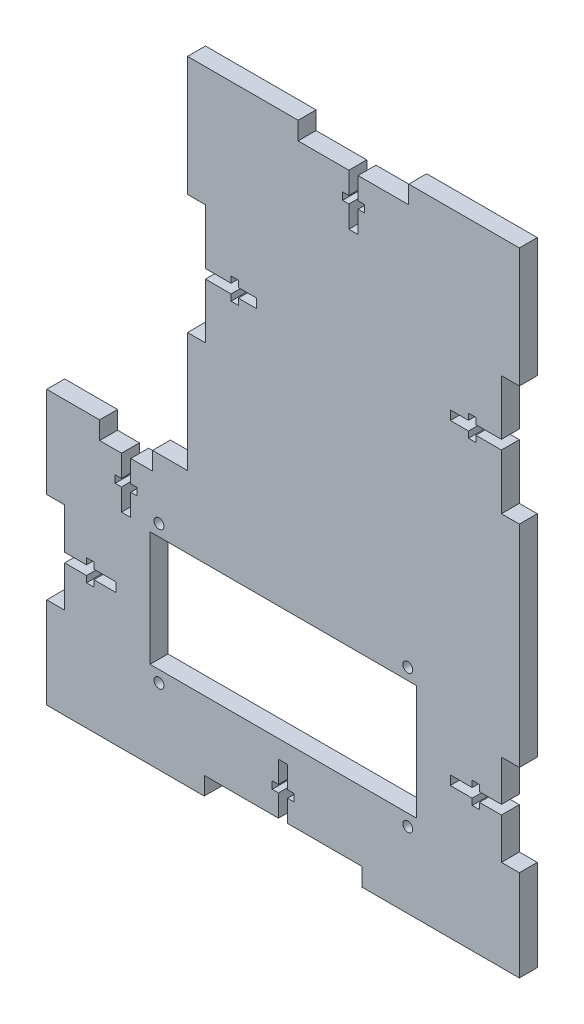
SolidWorks part; units mm, degrees
ref_plane "Front Plane" through (0, 0, 0) normal (0, 0, 1) x (1, 0, 0)
ref_plane "Top Plane" through (0, 0, 0) normal (0, 1, 0) x (1, 0, 0)
ref_plane "Right Plane" through (0, 0, 0) normal (1, 0, 0) x (0, 0, -1)
sketch "Sketch1" plane through (0, 0, 0) normal (0, 0, 1) x (1, 0, 0)
  line L1 (-66.929, -38.735) -> (66.929, -38.735)
  line L2 (-66.929, -38.735) -> (-66.929, 38.735)
  line L3 (-66.929, 38.735) -> (66.929, 38.735)
  line L4 (66.929, -38.735) -> (66.929, 38.735)
  line L5 (-66.929, -38.735) -> (66.929, 38.735) construction
  line L6 (-66.929, 38.735) -> (66.929, -38.735) construction
  point P0 (0, 0)
  dimension "D1" = 133.858
  dimension "D2" = 77.47
extrude "Boss-Extrude1" add sketch "Sketch1" along normal blind 5.08
sketch "Sketch2" plane through (0, 0, 5.08) normal (0, 0, 1) x (1, 0, 0)
  line L1 (-51.943, 38.735) -> (-36.957, 38.735)
  line L2 (-51.943, 38.735) -> (-51.943, 33.655)
  line L3 (-51.943, 33.655) -> (-36.957, 33.655)
  line L4 (-36.957, 38.735) -> (-36.957, 33.655)
  line L5 (66.929, 38.735) -> (-66.929, 38.735) construction
  line L6 (0, 0) -> (66.929, 0) construction
  line L7 (66.929, -38.735) -> (66.929, 38.735) construction
  dimension "D1" = 14.986
  dimension "D2" = 5.08
  dimension "D3" = 14.986
extrude "Cut-Extrude1" cut sketch "Sketch2" against normal through all
sketch "Sketch3" plane through (0, 0, 5.08) normal (0, 0, 1) x (1, 0, 0)
  line L0 (-66.929, 38.735) -> (-66.929, -38.735) construction
  line L1 (-66.929, 12.9117) -> (-61.849, 12.9117)
  line L2 (-66.929, 12.9117) -> (-66.929, -12.9117)
  line L3 (-66.929, -12.9117) -> (-61.849, -12.9117)
  line L4 (-61.849, 12.9117) -> (-61.849, -12.9117)
  line L5 (0, 0) -> (0, 39.951) construction
  line L6 (66.929, -12.9117) -> (61.849, -12.9117)
  line L7 (66.929, 12.9117) -> (66.929, -12.9117)
  line L8 (66.929, 12.9117) -> (61.849, 12.9117)
  line L9 (61.849, 12.9117) -> (61.849, -12.9117)
  dimension "D1" = 5.08
  dimension "D2" = 25.8233
  dimension "D3" = 25.8233
extrude "Cut-Extrude2" cut sketch "Sketch3" against normal through all
sketch "Sketch4" plane through (0, 0, 5.08) normal (0, 0, 1) x (1, 0, 0)
  line L0 (0, 0) -> (-61.849, 0) construction
  line L1 (-61.849, -12.9117) -> (-61.849, 12.9117) construction
  line L2 (0, 0) -> (0, 28.5152) construction
  line L3 (-61.849, 1.3017) -> (-47.371, 1.3017)
  line L4 (-61.849, 1.3017) -> (-61.849, -1.3018)
  line L5 (-61.849, -1.3018) -> (-47.371, -1.3018)
  line L6 (-47.371, 1.3017) -> (-47.371, -1.3018)
  line L7 (47.371, 1.3018) -> (47.371, -1.3018)
  line L8 (61.849, -1.3017) -> (47.371, -1.3018)
  line L9 (61.849, 1.3017) -> (61.849, -1.3017)
  line L10 (61.849, 1.3017) -> (47.371, 1.3018)
  line L11 (-66.929, -12.9117) -> (-66.929, 12.9117) construction
  point P9 (-47.371, 0)
  dimension "D1" = 1.3017
  dimension "D2" = 19.558
extrude "Cut-Extrude3" cut sketch "Sketch4" against normal through all
sketch "Sketch5" plane through (0, 0, 5.08) normal (0, 0, 1) x (1, 0, 0)
  line L0 (-44.45, 33.655) -> (-44.45, 4.7969) construction
  line L1 (-51.943, 33.655) -> (-36.957, 33.655) construction
  line L2 (0, 0) -> (35.9654, 0) construction
  line L3 (-43.1483, 33.655) -> (-45.7518, 33.655)
  line L4 (-43.1483, 33.655) -> (-43.1483, 19.177)
  line L5 (-43.1483, 19.177) -> (-45.7518, 19.177)
  line L6 (-45.7518, 33.655) -> (-45.7518, 19.177)
  point P11 (-44.45, 33.655)
  dimension "D1" = 2.6035
  dimension "D3" = 14.478
extrude "Cut-Extrude4" cut sketch "Sketch5" against normal through all
sketch "Sketch6" plane through (0, 0, 5.08) normal (0, 0, 1) x (1, 0, 0)
  line L0 (-54.61, 1.3017) -> (-54.61, -1.3018) construction
  line L1 (-47.371, 1.3017) -> (-61.849, 1.3017) construction
  line L2 (-61.849, -1.3018) -> (-47.371, -1.3018) construction
  line L3 (-43.1483, 26.416) -> (-45.7518, 26.416) construction
  line L4 (-43.1483, 33.655) -> (-43.1483, 19.177) construction
  line L5 (-45.7518, 19.177) -> (-45.7518, 33.655) construction
  line L6 (-43.1483, 26.416) -> (-47.5361, 26.416) construction
  line L7 (-47.5361, 27.4574) -> (-41.3639, 27.4574)
  line L8 (-47.5361, 27.4574) -> (-47.5361, 25.3746)
  line L9 (-47.5361, 25.3746) -> (-41.3639, 25.3746)
  line L10 (-41.3639, 27.4574) -> (-41.3639, 25.3746)
  line L11 (0, 0) -> (19.2929, 0) construction
  line L12 (0, 0) -> (0, 14.5303) construction
  line L17 (-54.61, -1.3018) -> (-54.61, -3.0861) construction
  line L18 (-55.6514, 3.0861) -> (-53.5686, 3.0861)
  line L19 (-55.6514, 3.0861) -> (-55.6514, -3.0861)
  line L20 (-55.6514, -3.0861) -> (-53.5686, -3.0861)
  line L21 (-53.5686, 3.0861) -> (-53.5686, -3.0861)
  line L22 (-44.45, 19.177) -> (-44.45, 25.3746) construction
  line L23 (-43.1483, 19.177) -> (-45.7518, 19.177) construction
  line L24 (-47.371, 0) -> (-53.5686, 0) construction
  line L25 (-47.371, -1.3018) -> (-47.371, 1.3017) construction
  line L26 (55.6514, -3.0861) -> (53.5686, -3.0861)
  line L27 (53.5686, 3.0861) -> (53.5686, -3.0861)
  line L28 (55.6514, 3.0861) -> (55.6514, -3.0861)
  line L29 (55.6514, 3.0861) -> (53.5686, 3.0861)
  dimension "D1" = 6.1722
  dimension "D2" = 2.0828
  dimension "D3" = 2.0828
  dimension "D4" = 6.1722
extrude "Cut-Extrude5" cut sketch "Sketch6" against normal through all
sketch "Sketch7" plane through (0, 0, 5.08) normal (0, 0, 1) x (1, 0, 0)
  line L0 (66.929, 38.735) -> (66.929, 140.335)
  line L1 (66.929, 140.335) -> (-27.051, 140.335)
  line L2 (-27.051, 140.335) -> (-27.051, 38.735)
  line L3 (66.929, 38.735) -> (-36.957, 38.735) construction
  line L60 (-43.1483, 27.4574) -> (-41.3639, 27.4574)
  line L61 (-41.3639, 27.4574) -> (-41.3639, 25.3746)
  line L62 (-41.3639, 25.3746) -> (-43.1483, 25.3746)
  line L63 (-43.1483, 19.177) -> (-45.7518, 19.177)
  line L64 (-45.7518, 25.3746) -> (-47.5361, 25.3746)
  line L65 (-47.5361, 25.3746) -> (-47.5361, 27.4574)
  line L66 (-47.5361, 27.4574) -> (-45.7518, 27.4574)
  line L67 (-45.7518, 33.655) -> (-51.943, 33.655)
  line L68 (-43.1483, 33.655) -> (-43.1483, 27.4574)
  line L70 (-43.1483, 25.3746) -> (-43.1483, 19.177)
  line L72 (61.849, -1.3018) -> (55.6514, -1.3018)
  line L73 (55.6514, -1.3018) -> (55.6514, -3.0861)
  line L74 (55.6514, -3.0861) -> (53.5686, -3.0861)
  line L75 (53.5686, -3.0861) -> (53.5686, -1.3017)
  line L76 (53.5686, -1.3017) -> (47.371, -1.3017)
  line L77 (47.371, -1.3017) -> (47.371, 1.3018)
  line L78 (47.371, 1.3018) -> (53.5686, 1.3018)
  line L79 (53.5686, 1.3018) -> (53.5686, 3.0861)
  line L80 (53.5686, 3.0861) -> (55.6514, 3.0861)
  line L81 (55.6514, 3.0861) -> (55.6514, 1.3018)
  line L82 (55.6514, 1.3018) -> (61.849, 1.3018)
  line L83 (61.849, 1.3018) -> (61.849, 12.9117)
  line L84 (61.849, 12.9117) -> (66.929, 12.9117)
  line L85 (66.929, 12.9117) -> (66.929, 38.735)
  line L86 (66.929, 38.735) -> (-36.957, 38.735)
  line L87 (-36.957, 38.735) -> (-36.957, 33.655)
  line L88 (-36.957, 33.655) -> (-43.1483, 33.655)
  line L89 (-45.7518, 19.177) -> (-45.7518, 25.3746)
  line L91 (-45.7518, 27.4574) -> (-45.7518, 33.655)
  line L101 (-51.943, 33.655) -> (-51.943, 38.735)
  line L102 (-51.943, 38.735) -> (-66.929, 38.735)
  line L103 (-66.929, 38.735) -> (-66.929, 12.9117)
  line L104 (-66.929, 12.9117) -> (-61.849, 12.9117)
  line L105 (-61.849, 12.9117) -> (-61.849, 1.3017)
  line L106 (-61.849, 1.3017) -> (-55.6514, 1.3017)
  line L107 (-55.6514, 1.3017) -> (-55.6514, 3.0861)
  line L108 (-55.6514, 3.0861) -> (-53.5686, 3.0861)
  line L109 (-53.5686, 3.0861) -> (-53.5686, 1.3017)
  line L110 (-53.5686, 1.3017) -> (-47.371, 1.3017)
  line L111 (-47.371, 1.3017) -> (-47.371, -1.3018)
  line L112 (-47.371, -1.3018) -> (-53.5686, -1.3018)
  line L113 (-53.5686, -1.3018) -> (-53.5686, -3.0861)
  line L114 (-53.5686, -3.0861) -> (-55.6514, -3.0861)
  line L115 (-55.6514, -3.0861) -> (-55.6514, -1.3018)
  line L116 (-55.6514, -1.3018) -> (-61.849, -1.3018)
  line L117 (-61.849, -1.3018) -> (-61.849, -12.9117)
  line L118 (-61.849, -12.9117) -> (-66.929, -12.9117)
  line L119 (-66.929, -12.9117) -> (-66.929, -38.735)
  line L120 (-66.929, -38.735) -> (66.929, -38.735)
  line L137 (66.929, -38.735) -> (66.929, -12.9117)
  line L138 (66.929, -12.9117) -> (61.849, -12.9117)
  line L139 (61.849, -12.9117) -> (61.849, -1.3018)
  line L154 (66.929, 38.735) -> (-27.051, 38.735)
  dimension "D1" = 101.6
  dimension "D2" = 93.98
  dimension "D3" = 0
extrude "Boss-Extrude2" add sketch "Sketch7" against normal blind 5.08
sketch "Sketch8" plane through (0, 0, 5.08) normal (0, 0, 1) x (1, 0, 0)
  line L0 (-66.929, -38.735) -> (66.929, -38.735) construction
  line L1 (22.3097, -38.735) -> (-22.3097, -38.735)
  line L2 (22.3097, -38.735) -> (22.3097, -33.655)
  line L3 (22.3097, -33.655) -> (-22.3097, -33.655)
  line L4 (-22.3097, -38.735) -> (-22.3097, -33.655)
  dimension "D1" = 5.08
  dimension "D2" = 44.6193
  dimension "D3" = 44.6193
extrude "Cut-Extrude6" cut sketch "Sketch8" against normal through all
sketch "Sketch10" plane through (0, 0, 5.08) normal (0, 0, 1) x (1, 0, 0)
  line L0 (22.3097, -33.655) -> (-22.3097, -33.655) construction
  line L1 (1.3018, -33.655) -> (-1.3018, -33.655)
  line L2 (1.3018, -33.655) -> (1.3017, -19.177)
  line L3 (1.3017, -19.177) -> (-1.3018, -19.177)
  line L4 (-1.3018, -33.655) -> (-1.3018, -19.177)
  line L5 (0, -19.177) -> (0, 0) construction
  dimension "D1" = 2.6035
  dimension "D2" = 14.478
extrude "Cut-Extrude7" cut sketch "Sketch10" against normal through all
sketch "Sketch11" plane through (0, 0, 5.08) normal (0, 0, 1) x (1, 0, 0)
  line L0 (3.0861, -26.416) -> (3.0861, -33.655) construction
  line L1 (22.3097, -33.655) -> (1.3018, -33.655) construction
  line L2 (-3.0861, -25.3746) -> (3.0861, -25.3746)
  line L3 (-3.0861, -25.3746) -> (-3.0861, -27.4574)
  line L4 (-3.0861, -27.4574) -> (3.0861, -27.4574)
  line L5 (3.0861, -25.3746) -> (3.0861, -27.4574)
  line L6 (-1.3018, -19.177) -> (-1.3017, -33.655) construction
  point P8 (-1.3017, -27.4574)
  dimension "D1" = 2.0828
  dimension "D2" = 6.1722
  dimension "D3" = 7.239
  dimension "D4" = 1.7844
extrude "Cut-Extrude8" cut sketch "Sketch11" against normal through all
sketch "Sketch12" plane through (0, 0, 5.08) normal (0, 0, 1) x (1, 0, 0)
  line L0 (66.929, 12.9117) -> (66.929, 140.335) construction
  line L1 (66.929, 72.6017) -> (61.849, 72.6017)
  line L2 (66.929, 72.6017) -> (66.929, 106.4683)
  line L3 (66.929, 106.4683) -> (61.849, 106.4683)
  line L4 (61.849, 72.6017) -> (61.849, 106.4683)
  line L5 (19.939, 140.335) -> (19.939, 42.6911) construction
  line L6 (66.929, 140.335) -> (-27.051, 140.335) construction
  line L7 (-21.971, 72.6017) -> (-21.971, 106.4683)
  line L8 (-27.051, 106.4683) -> (-21.971, 106.4683)
  line L9 (-27.051, 72.6017) -> (-27.051, 106.4683)
  line L10 (-27.051, 72.6017) -> (-21.971, 72.6017)
  dimension "D1" = 5.08
  dimension "D2" = 33.8667
  dimension "D3" = 33.8667
extrude "Cut-Extrude9" cut sketch "Sketch12" against normal through all
sketch "Sketch13" plane through (0, 0, 5.08) normal (0, 0, 1) x (1, 0, 0)
  line L0 (47.371, 89.535) -> (61.849, 89.535) construction
  line L1 (61.849, 106.4683) -> (61.849, 72.6017) construction
  line L2 (19.939, 140.335) -> (19.939, 63.8669) construction
  line L3 (66.929, 140.335) -> (-27.051, 140.335) construction
  line L4 (-21.971, 88.2332) -> (-21.971, 90.8367)
  line L5 (47.371, 88.2332) -> (61.849, 88.2332)
  line L6 (47.371, 88.2332) -> (47.371, 90.8367)
  line L7 (47.371, 90.8367) -> (61.849, 90.8367)
  line L8 (61.849, 88.2332) -> (61.849, 90.8367)
  line L9 (-7.493, 90.8367) -> (-21.971, 90.8367)
  line L10 (-7.493, 88.2332) -> (-7.493, 90.8367)
  line L11 (-7.493, 88.2332) -> (-21.971, 88.2332)
  line L12 (19.939, 130.1398) -> (19.939, 140.335) construction
  line L13 (21.2407, 140.335) -> (18.6373, 140.335)
  line L14 (21.2407, 140.335) -> (21.2408, 120.777)
  line L15 (21.2408, 120.777) -> (18.6373, 120.777)
  line L16 (18.6373, 140.335) -> (18.6373, 120.777)
  dimension "D1" = 2.6035
  dimension "D2" = 14.478
  dimension "D3" = 2.6035
  dimension "D4" = 19.558
extrude "Cut-Extrude10" cut sketch "Sketch13" against normal through all
sketch "Sketch14" plane through (0, 0, 5.08) normal (0, 0, 1) x (1, 0, 0)
  line L0 (54.61, 93.7894) -> (61.849, 93.7894) construction
  line L1 (54.61, 86.4489) -> (52.5272, 86.4489)
  line L2 (54.61, 86.4489) -> (54.61, 92.6211)
  line L3 (54.61, 92.6211) -> (52.5272, 92.6211)
  line L4 (52.5272, 86.4489) -> (52.5272, 92.6211)
  line L5 (61.849, 106.4683) -> (61.849, 90.8367) construction
  line L6 (61.849, 90.8367) -> (47.371, 90.8367) construction
  line L7 (19.939, 140.335) -> (19.939, -38.735) construction
  line L9 (-14.732, 92.6211) -> (-12.6492, 92.6211)
  line L10 (-14.732, 86.4489) -> (-14.732, 92.6211)
  line L11 (-12.6492, 86.4489) -> (-12.6492, 92.6211)
  line L12 (-14.732, 86.4489) -> (-12.6492, 86.4489)
  line L14 (21.2407, 140.335) -> (18.6373, 140.335) construction
  line L15 (18.6373, 140.335) -> (18.6373, 120.777) construction
  line L16 (23.0251, 126.9746) -> (16.8529, 126.9746)
  line L17 (23.0251, 126.9746) -> (23.0251, 129.0574)
  line L18 (23.0251, 129.0574) -> (16.8529, 129.0574)
  line L19 (16.8529, 126.9746) -> (16.8529, 129.0574)
  line L20 (16.8529, 128.016) -> (16.8529, 140.335) construction
  line L21 (18.6373, 140.335) -> (-27.051, 140.335) construction
  point P8 (52.5272, 90.8367)
  point P25 (18.6373, 126.9746)
  dimension "D1" = 2.0828
  dimension "D2" = 6.1722
  dimension "D3" = 7.239
  dimension "D4" = 1.7844
  dimension "D5" = 2.0828
  dimension "D6" = 6.1722
  dimension "D7" = 1.7844
  dimension "D8" = 12.319
extrude "Cut-Extrude11" cut sketch "Sketch14" against normal through all
sketch "Sketch15" plane through (0, 0, 5.08) normal (0, 0, 1) x (1, 0, 0)
  line L0 (66.929, 140.335) -> (21.2407, 140.335) construction
  line L1 (35.6023, 140.335) -> (4.2757, 140.335)
  line L2 (35.6023, 140.335) -> (35.6023, 135.255)
  line L3 (35.6023, 135.255) -> (4.2757, 135.255)
  line L4 (4.2757, 140.335) -> (4.2757, 135.255)
  dimension "D1" = 5.08
  dimension "D2" = 31.3267
  dimension "D3" = 31.3267
extrude "Cut-Extrude12" cut sketch "Sketch15" against normal through all
sketch "Sketch16" plane through (0, 0, 0) normal (0, 0, 1) x (1, 0, 0)
  line L0 (-52.9108, 11.4879) -> (-37.6708, 11.4879) construction
  line L1 (-37.6708, 18.4166) -> (37.7672, 18.4166)
  line L2 (-37.6708, 18.4166) -> (-37.6708, -14.0954)
  line L3 (-37.6708, -14.0954) -> (37.7672, -14.0954)
  line L4 (37.7672, 18.4166) -> (37.7672, -14.0954)
  line L6 (-15.4808, 48.8966) -> (-15.4808, 18.4166) construction
  line L8 (-35.1308, 21.7186) -> (-35.1308, 18.4166) construction
  line L9 (-37.6708, 2.1606) -> (37.7672, 2.1606) construction
  line L10 (35.3288, 21.7186) -> (35.3288, 18.4166) construction
  line L11 (-35.1308, 21.7186) -> (35.3288, 21.7186) construction
  circle A0 centre (-35.1308, 21.7186) radius 1.397
  circle A1 centre (35.3288, 21.7186) radius 1.397
  circle A2 centre (35.3288, -17.3974) radius 1.397
  circle A3 centre (-35.1308, -17.3974) radius 1.397
  dimension "D5" = 2.794
  dimension "D7" = 2.794
  dimension "D1" = 15.24
  dimension "D2" = 30.48
  dimension "D3" = 75.438
  dimension "D4" = 32.512
  dimension "D6" = 3.302
  dimension "D8" = 70.4596
  dimension "D9" = 2.54
extrude "Cut-Extrude14" cut sketch "Sketch16" against normal through all from surface starting at face at (1.6252, 44.3488, 5.08)
equation "\"Length\"= \"Length@Box.SLDASM\""
equation "\"D1@Sketch1\"  = \"Length\" + 2 * \"Material\""
equation "\"Width\"= \"Short Height@Box.SLDASM\""
equation "\"D2@Sketch1\" = \"Width\" + 2 * \"Material\""
equation "\"Material\"= \"Material@Box.SLDASM\""
equation "\"D1@Boss-Extrude1\" = \"Material\""
equation "\"D1@Sketch2\"=(\"Length\" -\"Over Hang@Box.SLDASM\"+\"Material\"*2)/3"
equation "\"D2@Sketch2\"= \"Material\""
equation "\"D3@Sketch2\"=(\"Length\" -\"Over Hang@Box.SLDASM\"+\"Material\"*2)/3"
equation "\"D1@Sketch3\"=\"Material\""
equation "\"D2@Sketch3\"=(\"Width\" +\"Material\"*2)/3"
equation "\"D3@Sketch3\"=(\"Width\" +\"Material\"*2)/3"
equation "\"Diameter of Screw\"= \"Diameter of Screw@Box.SLDASM\""
equation "\"Length of screw\"= \"Length of Screw@Box.SLDASM\""
equation "\"D3@Sketch5\"= \"Length of screw\" - \"Material\""
equation "\"D1@Sketch5\" = \"Diameter of Screw\""
equation "\"D1@Sketch4\"= \"Diameter of Screw\" /2"
equation "\"D2@Sketch4\"=\"Length of screw\""
equation "\"Diameter of Nut\"= \"Diameter of Nut@Box.SLDASM\""
equation "\"D1@Sketch6\"=\"Diameter of Nut\""
equation "\"Height of Nut\"= \"Height of Nut@Box.SLDASM\""
equation "\"D3@Sketch6\"= \"Height of Nut\""
equation "\"D4@Sketch6\"=\"Diameter of Nut\""
equation "\"D2@Sketch6\"=\"Height of Nut\""
equation "\"D1@Sketch7\"= \"Long Height@Box.SLDASM\"-\"Short Height@Box.SLDASM\""
equation "\"D2@Sketch7\" = \"Over Hang@Box.SLDASM\" + \"Material\""
equation "\"D1@Boss-Extrude2\" = \"Material\""
equation "\"D1@Sketch8\"= \"Material\""
equation "\"D2@Sketch8\"=(\"Length\" + \"Material\"*2)/3"
equation "\"D3@Sketch8\"=(\"Length\" + \"Material\"*2)/3"
equation "\"D1@Sketch10\"=\"Diameter of Screw\""
equation "\"D2@Sketch10\"=\"Length of screw\" - \"Material\""
equation "\"D3@Sketch11\" = ( \"Length of screw\" - \"Material\" ) / 2"
equation "\"D4@Sketch11\"= ( \"Diameter of Nut\"-\"Diameter of Screw\" )/2"
equation "\"D1@Sketch12\"=\"Material\""
equation "\"D2@Sketch12\"=(\"Long Height@Box.SLDASM\"-\"Short Height@Box.SLDASM\")/3"
equation "\"D3@Sketch12\"=(\"Long Height@Box.SLDASM\"-\"Short Height@Box.SLDASM\")/3"
equation "\"D1@Sketch13\"=\"Diameter of Screw\""
equation "\"D2@Sketch13\"=\"Length of screw\"-\"Material\""
equation "\"D1@Sketch14\"=\"Height of Nut\""
equation "\"D2@Sketch14\"=\"Diameter of Nut\""
equation "\"D3@Sketch14\"=(\"Length of screw\"-\"Material\")/2"
equation "\"D4@Sketch14\"=(\"Diameter of Nut\"-\"Diameter of Screw\")/2"
equation "\"D1@Sketch15\"= \"Material\""
equation "\"D2@Sketch15\"=(\"Material\"+ \"over hang@Box.SLDASM\" )/3"
equation "\"D3@Sketch15\"=(\"Material\" + \"over hang@Box.SLDASM\" )/3"
equation "\"D3@Sketch13\"=\"Diameter of Screw\""
equation "\"D4@Sketch13\"=\"Length of screw\""
equation "\"D5@Sketch14\"=\"Height of Nut\""
equation "\"D6@Sketch14\"=\"Diameter of Nut\""
equation "\"D7@Sketch14\"=(\"Diameter of Nut\"-\"Diameter of Screw\")/2"
equation "\"D8@Sketch14\"=(\"Length of screw\"-\"Material\")/2 + \"Material\""
